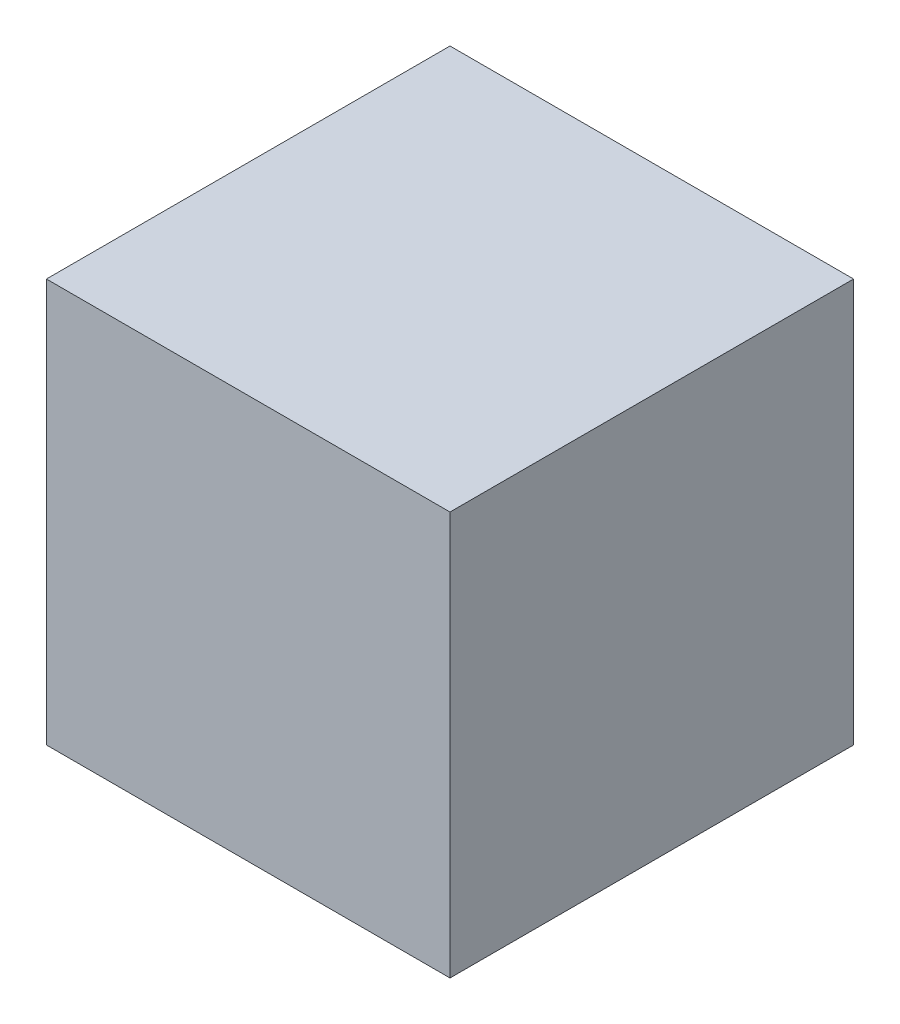
SolidWorks part; units mm, degrees
ref_plane "Front Plane" through (0, 0, 0) normal (0, 0, 1) x (1, 0, 0)
ref_plane "Top Plane" through (0, 0, 0) normal (0, 1, 0) x (1, 0, 0)
ref_plane "Right Plane" through (0, 0, 0) normal (1, 0, 0) x (0, 0, -1)
sketch "Sketch5" plane through (0, 0, 0) normal (1, 0, 0) x (0, 0, -1)
  line L0 (0, 0) -> (0, 1000)
  line L1 (0, 1000) -> (1000, 1000)
  line L2 (1000, 1000) -> (1000, 0)
  line L3 (1000, 0) -> (0, 0)
  dimension "D1" = 1000
  dimension "D2" = 1000
  dimension "D3" = 1000
extrude "Boss-Extrude2" add sketch "Sketch5" along normal blind 1000
ref_plane "Plane2" through (500, 0, 0) normal (1, 0, 0) x (0, 0, -1)
sketch "Sketch6" plane through (500, 0, 0) normal (1, 0, 0) x (0, 0, -1)
  line L0 (83.2, 500) -> (916.8, 500)
  arc A0 (83.2, 500) -> (916.8, 500) centre (500, 500) cw
revolve "Cut-Revolve5" cut sketch "Sketch6" angle 360 about L0
sketch "Sketch7" plane through (0, 0, 0) normal (1, 0, 0) x (0, 0, -1)
  line L0 (0, 500) -> (1000, 500)
  line L1 (0, 1000) -> (0, 0) construction
  line L2 (1000, 0) -> (1000, 1000) construction
  circle A0 centre (500, 500) radius 250
extrude "Cut-Extrude2" cut sketch "Sketch7" along normal blind 400 contours A0
